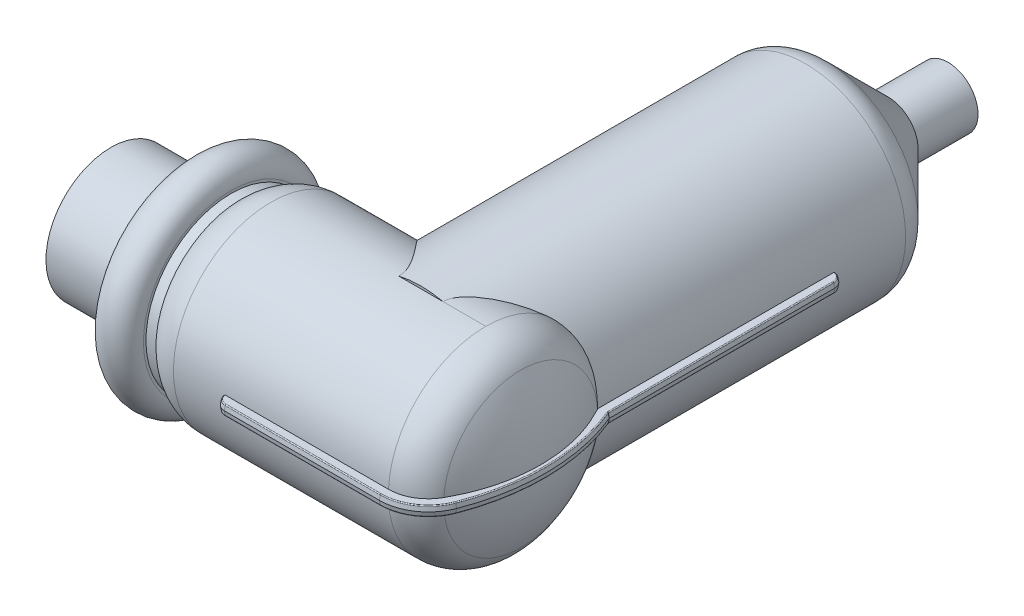
SolidWorks part; units mm, degrees
ref_plane "Front Plane" through (0, 0, 0) normal (0, 0, 1) x (1, 0, 0)
ref_plane "Top Plane" through (0, 0, 0) normal (0, 1, 0) x (1, 0, 0)
ref_plane "Right Plane" through (0, 0, 0) normal (1, 0, 0) x (0, 0, -1)
sketch "Sketch1" plane through (0, 0, 0) normal (0, 0, 1) x (1, 0, 0)
  line L0 (8, 6.5) -> (8, 8.75)
  line L2 (12, 8.75) -> (12, 8.5)
  line L3 (12, 8.5) -> (13, 8.5)
  line L4 (0, 0) -> (43, 0)
  line L5 (37.5, 9.75) -> (16, 9.75)
  line L6 (0, 0) -> (-5.7927, 0) construction
  line L7 (43, 0) -> (43, 7.3633) construction
  line L8 (8, 6.5) -> (0, 6.5)
  line L9 (0, 6.5) -> (0, 0)
  arc A0 (8, 8.75) -> (12, 8.75) centre (10, 8.75) cw
  arc A1 (16, 9.75) -> (13, 8.5) centre (16, 5.525) ccw
  arc A2 (43, 0) -> (40.9903, 7.704) centre (27.2292, 0) ccw
  arc A3 (37.5, 9.75) -> (40.9903, 7.704) centre (37.5, 5.75) cw
  dimension "D9" = 4
  dimension "D1" = 4
  dimension "D2" = 17.5
  dimension "D3" = 5
  dimension "D4" = 8
  dimension "D5" = 17
  dimension "D6" = 35
  dimension "D7" = 29.5
  dimension "D8" = 19.5
  dimension "D10" = 13
  dimension "D11" = 8
revolve "Revolve1" add sketch "Sketch1" angle 360 about L6
sketch "Sketch2" plane through (0, 0, 0) normal (0, 1, 0) x (1, 0, 0)
  line L0 (31, 0) -> (31, -17.9723) construction
  line L1 (31, 0) -> (0, 0) construction
  line L2 (41, 0) -> (31, 0)
  line L3 (31, 0) -> (31, 52.7426)
  line L4 (31, 52.7426) -> (34, 52.7426)
  line L5 (34, 52.7426) -> (34, 46.7426)
  line L6 (34, 46.7426) -> (40.1213, 40.6213)
  line L7 (41, 38.5) -> (41, 0)
  arc A0 (40.1213, 40.6213) -> (41, 38.5) centre (38, 38.5) cw
  dimension "D6" = 6
  dimension "D5" = 3
  dimension "D1" = 31
  dimension "D2" = 45
  dimension "D3" = 38.5
  dimension "D4" = 20
  dimension "D8" = 6
revolve "Revolve2" add sketch "Sketch2" angle 360 about L0
sketch "Sketch3" plane through (0, 0, 0) normal (0, 1, 0) x (1, 0, 0)
  line L0 (37.5, 6.1084) -> (37.5, -9.75) construction
  line L1 (40.9, 7.7447) -> (40.9, 31.5)
  line L2 (0, 0) -> (43, 0) construction
  line L3 (21, -9.65) -> (37.5, -9.65)
  line L4 (31, 0) -> (31, 52.7426) construction
  line L5 (21.1, 9.65) -> (18, 9.65)
  line L7 (21.1, 31.5) -> (21.1, 9.65)
  line L8 (21, 38.5) -> (41, 38.5) construction
  line L9 (16, -9.75) -> (16, 9.75) construction
  line L10 (22, -10.65) -> (37.5, -10.65)
  line L11 (41.9, 7.9447) -> (41.9, 30.5)
  line L12 (20.1, 30.5) -> (20.1, 10.65)
  line L13 (20.1, 10.65) -> (19, 10.65)
  line L14 (41.9, 7.9447) -> (41.9, 31.5) construction
  line L15 (20.1, 31.5) -> (20.1, 10.65) construction
  line L16 (20.1, 10.65) -> (18, 10.65) construction
  line L17 (21, -10.65) -> (37.5, -10.65) construction
  line L18 (31, 0) -> (0, 0) construction
  arc A0 (41.1395, -7.1516) -> (40.9, 7.7447) centre (22.5689, 0) ccw construction
  arc A1 (41.1395, -7.1516) -> (40.9, 7.7447) centre (22.5689, 0) ccw
  arc A3 (37.5, -9.65) -> (41.1395, -7.1516) centre (37.5, -5.75) ccw
  arc A4 (37.5, -10.65) -> (42.0726, -7.5109) centre (37.5, -5.75) ccw
  arc A5 (42.0726, -7.5109) -> (41.9, 7.9447) centre (22.5689, 0) ccw
  arc A6 (41.9, 30.5) -> (40.9, 31.5) centre (40.9, 30.5) ccw
  arc A7 (20.1, 30.5) -> (21.1, 31.5) centre (21.1, 30.5) cw
  arc A8 (19, 10.65) -> (18, 9.65) centre (19, 9.65) ccw
  arc A9 (22, -10.65) -> (21, -9.65) centre (22, -9.65) cw
  dimension "D11" = 3.9
  dimension "D12" = 19.9
  dimension "D1" = 7
  dimension "D2" = 7
  dimension "D3" = 2
  dimension "D4" = 5
  dimension "D7" = 9.9
  dimension "D8" = 9.65
  dimension "D9" = 9.9
  dimension "D10" = 9.65
  dimension "D5" = 1
  dimension "D6" = 1
extrude "Boss-Extrude1" add sketch "Sketch3" along normal mid plane 1 draft 10
fillet "Fillet1" radius 0.1 24 edges at (20.4248, 0.5, -31.1128) (20.4248, -0.5, -31.1128) (20.1882, 0.5, -20.5309) (20.1882, -0.5, -20.5309) (18.3872, -0.5, -10.3252) (19.5941, 0.5, -10.5618) (41.5752, 0.5, -31.1128) (21.3872, 0.5, 10.3252) (29.75, 0.5, 10.5618) (40.2233, 0.5, 9.717) (41.5752, -0.5, -31.1128) (43.3793, -0.5, -0.2412) (40.2233, -0.5, 9.717) (29.75, -0.5, 10.5618) (19.5941, -0.5, -10.5618) (20.1441, -0.25, -10.6059) (20.1441, 0.25, -10.6059) (18.3872, 0.5, -10.3252) (41.8118, 0.5, -19.2137) (43.3793, 0.5, -0.2412) (41.8118, -0.5, -19.2137) (21.3872, -0.5, 10.3252)
